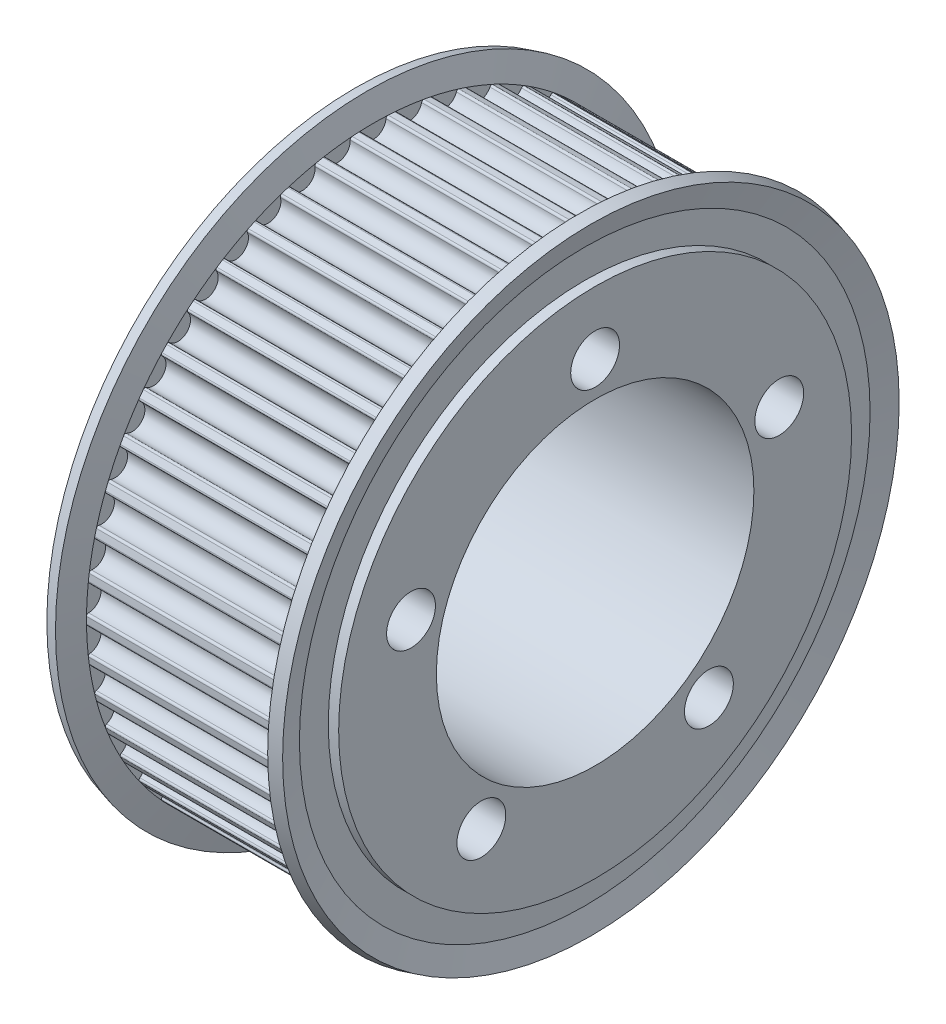
SolidWorks part; units mm, degrees
ref_plane "Front Plane" through (0, 0, 0) normal (0, 0, 1) x (1, 0, 0)
ref_plane "Top Plane" through (0, 0, 0) normal (0, 1, 0) x (1, 0, 0)
ref_plane "Right Plane" through (0, 0, 0) normal (1, 0, 0) x (0, 0, -1)
ref_plane "Plane1" through (0, 0, 0) normal (0, 0, 1) x (1, 0, 0)
sketch "Sketch1" plane through (0, 0, 0) normal (0, 0, 1) x (1, 0, 0)
  line L0 (0, 0) -> (0, 21)
  line L1 (0, 21) -> (0.85, 21)
  line L2 (0.85, 21) -> (0.85, 23.3633)
  line L3 (0.85, 23.3633) -> (0.3468, 25.2412)
  line L4 (0.3468, 25.2412) -> (1.3128, 25.5)
  line L5 (1.3128, 25.5) -> (1.85, 23.495)
  line L6 (1.85, 23.495) -> (18.15, 23.495)
  line L7 (18.15, 23.495) -> (18.6872, 25.5)
  line L8 (18.6872, 25.5) -> (19.6532, 25.2412)
  line L9 (19.6532, 25.2412) -> (19.15, 23.3633)
  line L10 (19.15, 23.3633) -> (19.15, 21)
  line L11 (19.15, 21) -> (20, 21)
  line L12 (20, 21) -> (20, 0)
  line L13 (20, 0) -> (0, 0)
  line L14 (20, 0) -> (0, 0) construction
revolve "Revolve1" add sketch "Sketch1" angle 360 about L14 reverse direction yes
ref_plane "Plane2" through (10, 0, 0) normal (1, 0, 0) x (0, 0, -1)
sketch "Sketch2" plane through (10, 0, 0) normal (1, 0, 0) x (0, 0, -1)
  line L0 (-1.2248, 23.8436) -> (-1.2053, 23.4641)
  line L1 (1.2053, 23.4641) -> (1.2248, 23.8436)
  arc A0 (-1.2053, 23.4641) -> (-1.0271, 23.3071) centre (-1.1966, 23.2943) cw
  arc A1 (-1.0271, 23.3071) -> (1.0271, 23.3071) centre (0, 23.385) ccw
  arc A2 (1.0271, 23.3071) -> (1.2053, 23.4641) centre (1.1966, 23.2943) cw
  arc A3 (1.2248, 23.8436) -> (-1.2248, 23.8436) centre (0, 0) ccw
extrude "Cut-Extrude1" cut sketch "Sketch2" against normal blind 8.15 and the other way blind 8.15
ref_plane "Plane3" through (10, 0, 0) normal (1, 0, 0) x (0, 0, -1)
sketch "Sketch3" plane through (10, 0, 0) normal (1, 0, 0) x (0, 0, -1)
  line L0 (-4.2035, 23.502) -> (-4.1366, 23.128)
  line L1 (-1.745, 23.4301) -> (-1.7733, 23.8091)
  arc A0 (-4.1366, 23.128) -> (-3.9401, 22.9946) centre (-4.1067, 22.9606) cw
  arc A1 (-3.9401, 22.9946) -> (-1.9022, 23.2521) centre (-2.9309, 23.2006) ccw
  arc A2 (-1.9022, 23.2521) -> (-1.745, 23.4301) centre (-1.7324, 23.2606) cw
  arc A3 (-1.7733, 23.8091) -> (-4.2035, 23.502) centre (0, 0) ccw
extrude "Cut-Extrude2" cut sketch "Sketch3" against normal blind 8.15 and the other way blind 8.15
ref_plane "Plane4" through (10, 0, 0) normal (1, 0, 0) x (0, 0, -1)
sketch "Sketch4" plane through (10, 0, 0) normal (1, 0, 0) x (0, 0, -1)
  line L0 (-7.116, 22.7899) -> (-7.0027, 22.4272)
  line L1 (-4.6679, 23.0266) -> (-4.7434, 23.3991)
  arc A0 (-7.0027, 22.4272) -> (-6.791, 22.3195) centre (-6.952, 22.2649) cw
  arc A1 (-6.791, 22.3195) -> (-4.8015, 22.8303) centre (-5.8156, 22.6503) ccw
  arc A2 (-4.8015, 22.8303) -> (-4.6679, 23.0266) centre (-4.6341, 22.86) cw
  arc A3 (-4.7434, 23.3991) -> (-7.116, 22.7899) centre (0, 0) ccw
extrude "Cut-Extrude3" cut sketch "Sketch4" against normal blind 8.15 and the other way blind 8.15
ref_plane "Plane5" through (10, 0, 0) normal (1, 0, 0) x (0, 0, -1)
sketch "Sketch5" plane through (10, 0, 0) normal (1, 0, 0) x (0, 0, -1)
  line L0 (-9.9162, 21.7183) -> (-9.7583, 21.3726)
  line L1 (-7.5171, 22.26) -> (-7.6386, 22.6201)
  arc A0 (-9.7583, 21.3726) -> (-9.5349, 21.2923) centre (-9.6877, 21.218) cw
  arc A1 (-9.5349, 21.2923) -> (-7.625, 22.0485) centre (-8.6086, 21.7428) ccw
  arc A2 (-7.625, 22.0485) -> (-7.5171, 22.26) centre (-7.4627, 22.099) cw
  arc A3 (-7.6386, 22.6201) -> (-9.9162, 21.7183) centre (0, 0) ccw
extrude "Cut-Extrude4" cut sketch "Sketch5" against normal blind 8.15 and the other way blind 8.15
ref_plane "Plane6" through (10, 0, 0) normal (1, 0, 0) x (0, 0, -1)
sketch "Sketch6" plane through (10, 0, 0) normal (1, 0, 0) x (0, 0, -1)
  line L0 (-12.56, 20.3042) -> (-12.3601, 19.9811)
  line L1 (-10.2477, 21.1424) -> (-10.4134, 21.4843)
  arc A0 (-12.3601, 19.9811) -> (-12.1283, 19.9294) centre (-12.2707, 19.8365) cw
  arc A1 (-12.1283, 19.9294) -> (-10.3283, 20.919) centre (-11.2658, 20.4924) ccw
  arc A2 (-10.3283, 20.919) -> (-10.2477, 21.1424) centre (-10.1735, 20.9894) cw
  arc A3 (-10.4134, 21.4843) -> (-12.56, 20.3042) centre (0, 0) ccw
extrude "Cut-Extrude5" cut sketch "Sketch6" against normal blind 8.15 and the other way blind 8.15
ref_plane "Plane7" through (10, 0, 0) normal (1, 0, 0) x (0, 0, -1)
sketch "Sketch7" plane through (10, 0, 0) normal (1, 0, 0) x (0, 0, -1)
  line L0 (-15.0058, 18.5699) -> (-14.7669, 18.2744)
  line L1 (-12.8167, 19.6913) -> (-13.024, 20.0098)
  arc A0 (-14.7669, 18.2744) -> (-14.5305, 18.2522) centre (-14.6601, 18.1422) cw
  arc A1 (-14.5305, 18.2522) -> (-12.8687, 19.4596) centre (-13.7454, 18.9189) ccw
  arc A2 (-12.8687, 19.4596) -> (-12.8167, 19.6913) centre (-12.724, 19.5488) cw
  arc A3 (-13.024, 20.0098) -> (-15.0058, 18.5699) centre (0, 0) ccw
extrude "Cut-Extrude6" cut sketch "Sketch7" against normal blind 8.15 and the other way blind 8.15
ref_plane "Plane8" through (10, 0, 0) normal (1, 0, 0) x (0, 0, -1)
sketch "Sketch8" plane through (10, 0, 0) normal (1, 0, 0) x (0, 0, -1)
  line L0 (-17.2149, 16.5428) -> (-16.9409, 16.2795)
  line L1 (-15.1836, 17.9296) -> (-15.4292, 18.2196)
  arc A0 (-16.9409, 16.2795) -> (-16.7035, 16.2871) centre (-16.8183, 16.1617) cw
  arc A1 (-16.7035, 16.2871) -> (-15.2061, 17.6932) centre (-16.0081, 17.0469) ccw
  arc A2 (-15.2061, 17.6932) -> (-15.1836, 17.9296) centre (-15.0738, 17.7999) cw
  arc A3 (-15.4292, 18.2196) -> (-17.2149, 16.5428) centre (0, 0) ccw
extrude "Cut-Extrude7" cut sketch "Sketch8" against normal blind 8.15 and the other way blind 8.15
ref_plane "Plane9" through (10, 0, 0) normal (1, 0, 0) x (0, 0, -1)
sketch "Sketch9" plane through (10, 0, 0) normal (1, 0, 0) x (0, 0, -1)
  line L0 (-19.1525, 14.2547) -> (-18.8477, 14.0279)
  line L1 (-17.3111, 15.8852) -> (-17.5911, 16.1422)
  arc A0 (-18.8477, 14.0279) -> (-18.6131, 14.0652) centre (-18.7113, 13.9264) cw
  arc A1 (-18.6131, 14.0652) -> (-17.3038, 15.6479) centre (-18.0185, 14.9062) ccw
  arc A2 (-17.3038, 15.6479) -> (-17.3111, 15.8852) centre (-17.1858, 15.7703) cw
  arc A3 (-17.5911, 16.1422) -> (-19.1525, 14.2547) centre (0, 0) ccw
extrude "Cut-Extrude8" cut sketch "Sketch9" against normal blind 8.15 and the other way blind 8.15
ref_plane "Plane10" through (10, 0, 0) normal (1, 0, 0) x (0, 0, -1)
sketch "Sketch10" plane through (10, 0, 0) normal (1, 0, 0) x (0, 0, -1)
  line L0 (-20.7881, 11.7419) -> (-20.4572, 11.555)
  line L1 (-19.1655, 13.5903) -> (-19.4755, 13.8101)
  arc A0 (-20.4572, 11.555) -> (-20.2292, 11.6214) centre (-20.3092, 11.4714) cw
  arc A1 (-20.2292, 11.6214) -> (-19.1285, 13.3558) centre (-19.7446, 12.5303) ccw
  arc A2 (-19.1285, 13.3558) -> (-19.1655, 13.5903) centre (-19.0269, 13.492) cw
  arc A3 (-19.4755, 13.8101) -> (-20.7881, 11.7419) centre (0, 0) ccw
extrude "Cut-Extrude9" cut sketch "Sketch10" against normal blind 8.15 and the other way blind 8.15
ref_plane "Plane11" through (10, 0, 0) normal (1, 0, 0) x (0, 0, -1)
sketch "Sketch11" plane through (10, 0, 0) normal (1, 0, 0) x (0, 0, -1)
  line L0 (-22.0958, 9.0439) -> (-21.7441, 8.8999)
  line L1 (-20.7177, 11.0811) -> (-21.0528, 11.2603)
  arc A0 (-21.7441, 8.8999) -> (-21.5262, 8.9944) centre (-21.5868, 8.8355) cw
  arc A1 (-21.5262, 8.9944) -> (-20.6516, 10.853) centre (-21.1594, 9.9568) ccw
  arc A2 (-20.6516, 10.853) -> (-20.7177, 11.0811) centre (-20.5678, 11.0009) cw
  arc A3 (-21.0528, 11.2603) -> (-22.0958, 9.0439) centre (0, 0) ccw
extrude "Cut-Extrude10" cut sketch "Sketch11" against normal blind 8.15 and the other way blind 8.15
ref_plane "Plane12" through (10, 0, 0) normal (1, 0, 0) x (0, 0, -1)
sketch "Sketch12" plane through (10, 0, 0) normal (1, 0, 0) x (0, 0, -1)
  line L0 (-23.0551, 6.2032) -> (-22.6881, 6.1045)
  line L1 (-21.9432, 8.3971) -> (-22.2981, 8.5329)
  arc A0 (-22.6881, 6.1045) -> (-22.4838, 6.2255) centre (-22.5239, 6.0603) cw
  arc A1 (-22.4838, 6.2255) -> (-21.849, 8.1791) centre (-22.2405, 7.2264) ccw
  arc A2 (-21.849, 8.1791) -> (-21.9432, 8.3971) centre (-21.7844, 8.3363) cw
  arc A3 (-22.2981, 8.5329) -> (-23.0551, 6.2032) centre (0, 0) ccw
extrude "Cut-Extrude11" cut sketch "Sketch12" against normal blind 8.15 and the other way blind 8.15
ref_plane "Plane13" through (10, 0, 0) normal (1, 0, 0) x (0, 0, -1)
sketch "Sketch13" plane through (10, 0, 0) normal (1, 0, 0) x (0, 0, -1)
  line L0 (-23.6507, 3.2648) -> (-23.2743, 3.2128)
  line L1 (-22.8226, 5.5807) -> (-23.1917, 5.6709)
  arc A0 (-23.2743, 3.2128) -> (-23.0868, 3.3585) centre (-23.1059, 3.1895) cw
  arc A1 (-23.0868, 3.3585) -> (-22.7019, 5.3762) centre (-22.9708, 4.3819) ccw
  arc A2 (-22.7019, 5.3762) -> (-22.8226, 5.5807) centre (-22.6575, 5.5403) cw
  arc A3 (-23.1917, 5.6709) -> (-23.6507, 3.2648) centre (0, 0) ccw
extrude "Cut-Extrude12" cut sketch "Sketch13" against normal blind 8.15 and the other way blind 8.15
ref_plane "Plane14" through (10, 0, 0) normal (1, 0, 0) x (0, 0, -1)
sketch "Sketch14" plane through (10, 0, 0) normal (1, 0, 0) x (0, 0, -1)
  line L0 (-23.8734, 0.2748) -> (-23.4934, 0.2704)
  line L1 (-23.3421, 2.6762) -> (-23.7196, 2.7195)
  arc A0 (-23.4934, 0.2704) -> (-23.3256, 0.4384) centre (-23.3235, 0.2685) cw
  arc A1 (-23.3256, 0.4384) -> (-23.1967, 2.4885) centre (-23.3389, 1.4684) ccw
  arc A2 (-23.1967, 2.4885) -> (-23.3421, 2.6762) centre (-23.1732, 2.6569) cw
  arc A3 (-23.7196, 2.7195) -> (-23.8734, 0.2748) centre (0, 0) ccw
extrude "Cut-Extrude13" cut sketch "Sketch14" against normal blind 8.15 and the other way blind 8.15
ref_plane "Plane15" through (10, 0, 0) normal (1, 0, 0) x (0, 0, -1)
sketch "Sketch15" plane through (10, 0, 0) normal (1, 0, 0) x (0, 0, -1)
  line L0 (-23.7196, -2.7195) -> (-23.3421, -2.6762)
  line L1 (-23.4934, -0.2704) -> (-23.8734, -0.2748)
  arc A0 (-23.3421, -2.6762) -> (-23.1967, -2.4885) centre (-23.1732, -2.6569) cw
  arc A1 (-23.1967, -2.4885) -> (-23.3256, -0.4384) centre (-23.3389, -1.4684) ccw
  arc A2 (-23.3256, -0.4384) -> (-23.4934, -0.2704) centre (-23.3235, -0.2685) cw
  arc A3 (-23.8734, -0.2748) -> (-23.7196, -2.7195) centre (0, 0) ccw
extrude "Cut-Extrude14" cut sketch "Sketch15" against normal blind 8.15 and the other way blind 8.15
ref_plane "Plane16" through (10, 0, 0) normal (1, 0, 0) x (0, 0, -1)
sketch "Sketch16" plane through (10, 0, 0) normal (1, 0, 0) x (0, 0, -1)
  line L0 (-23.1917, -5.6709) -> (-22.8226, -5.5807)
  line L1 (-23.2743, -3.2128) -> (-23.6507, -3.2648)
  arc A0 (-22.8226, -5.5807) -> (-22.7019, -5.3762) centre (-22.6575, -5.5403) cw
  arc A1 (-22.7019, -5.3762) -> (-23.0868, -3.3585) centre (-22.9708, -4.3819) ccw
  arc A2 (-23.0868, -3.3585) -> (-23.2743, -3.2128) centre (-23.1059, -3.1895) cw
  arc A3 (-23.6507, -3.2648) -> (-23.1917, -5.6709) centre (0, 0) ccw
extrude "Cut-Extrude15" cut sketch "Sketch16" against normal blind 8.15 and the other way blind 8.15
ref_plane "Plane17" through (10, 0, 0) normal (1, 0, 0) x (0, 0, -1)
sketch "Sketch17" plane through (10, 0, 0) normal (1, 0, 0) x (0, 0, -1)
  line L0 (-22.2981, -8.5329) -> (-21.9432, -8.3971)
  line L1 (-22.6881, -6.1045) -> (-23.0551, -6.2032)
  arc A0 (-21.9432, -8.3971) -> (-21.849, -8.1791) centre (-21.7844, -8.3363) cw
  arc A1 (-21.849, -8.1791) -> (-22.4838, -6.2255) centre (-22.2405, -7.2264) ccw
  arc A2 (-22.4838, -6.2255) -> (-22.6881, -6.1045) centre (-22.5239, -6.0603) cw
  arc A3 (-23.0551, -6.2032) -> (-22.2981, -8.5329) centre (0, 0) ccw
extrude "Cut-Extrude16" cut sketch "Sketch17" against normal blind 8.15 and the other way blind 8.15
ref_plane "Plane18" through (10, 0, 0) normal (1, 0, 0) x (0, 0, -1)
sketch "Sketch18" plane through (10, 0, 0) normal (1, 0, 0) x (0, 0, -1)
  line L0 (-21.0528, -11.2603) -> (-20.7177, -11.0811)
  line L1 (-21.7441, -8.8999) -> (-22.0958, -9.0439)
  arc A0 (-20.7177, -11.0811) -> (-20.6516, -10.853) centre (-20.5678, -11.0009) cw
  arc A1 (-20.6516, -10.853) -> (-21.5262, -8.9944) centre (-21.1594, -9.9568) ccw
  arc A2 (-21.5262, -8.9944) -> (-21.7441, -8.8999) centre (-21.5868, -8.8355) cw
  arc A3 (-22.0958, -9.0439) -> (-21.0528, -11.2603) centre (0, 0) ccw
extrude "Cut-Extrude17" cut sketch "Sketch18" against normal blind 8.15 and the other way blind 8.15
ref_plane "Plane19" through (10, 0, 0) normal (1, 0, 0) x (0, 0, -1)
sketch "Sketch19" plane through (10, 0, 0) normal (1, 0, 0) x (0, 0, -1)
  line L0 (-19.4755, -13.8101) -> (-19.1655, -13.5903)
  line L1 (-20.4572, -11.555) -> (-20.7881, -11.7419)
  arc A0 (-19.1655, -13.5903) -> (-19.1285, -13.3558) centre (-19.0269, -13.492) cw
  arc A1 (-19.1285, -13.3558) -> (-20.2292, -11.6214) centre (-19.7446, -12.5303) ccw
  arc A2 (-20.2292, -11.6214) -> (-20.4572, -11.555) centre (-20.3092, -11.4714) cw
  arc A3 (-20.7881, -11.7419) -> (-19.4755, -13.8101) centre (0, 0) ccw
extrude "Cut-Extrude18" cut sketch "Sketch19" against normal blind 8.15 and the other way blind 8.15
ref_plane "Plane20" through (10, 0, 0) normal (1, 0, 0) x (0, 0, -1)
sketch "Sketch20" plane through (10, 0, 0) normal (1, 0, 0) x (0, 0, -1)
  line L0 (-17.5911, -16.1422) -> (-17.3111, -15.8852)
  line L1 (-18.8477, -14.0279) -> (-19.1525, -14.2547)
  arc A0 (-17.3111, -15.8852) -> (-17.3038, -15.6479) centre (-17.1858, -15.7703) cw
  arc A1 (-17.3038, -15.6479) -> (-18.6131, -14.0652) centre (-18.0185, -14.9062) ccw
  arc A2 (-18.6131, -14.0652) -> (-18.8477, -14.0279) centre (-18.7113, -13.9264) cw
  arc A3 (-19.1525, -14.2547) -> (-17.5911, -16.1422) centre (0, 0) ccw
extrude "Cut-Extrude19" cut sketch "Sketch20" against normal blind 8.15 and the other way blind 8.15
ref_plane "Plane21" through (10, 0, 0) normal (1, 0, 0) x (0, 0, -1)
sketch "Sketch21" plane through (10, 0, 0) normal (1, 0, 0) x (0, 0, -1)
  line L0 (-15.4292, -18.2196) -> (-15.1836, -17.9296)
  line L1 (-16.9409, -16.2795) -> (-17.2149, -16.5428)
  arc A0 (-15.1836, -17.9296) -> (-15.2061, -17.6932) centre (-15.0738, -17.7999) cw
  arc A1 (-15.2061, -17.6932) -> (-16.7035, -16.2871) centre (-16.0081, -17.0469) ccw
  arc A2 (-16.7035, -16.2871) -> (-16.9409, -16.2795) centre (-16.8183, -16.1617) cw
  arc A3 (-17.2149, -16.5428) -> (-15.4292, -18.2196) centre (0, 0) ccw
extrude "Cut-Extrude20" cut sketch "Sketch21" against normal blind 8.15 and the other way blind 8.15
ref_plane "Plane22" through (10, 0, 0) normal (1, 0, 0) x (0, 0, -1)
sketch "Sketch22" plane through (10, 0, 0) normal (1, 0, 0) x (0, 0, -1)
  line L0 (-13.024, -20.0098) -> (-12.8167, -19.6913)
  line L1 (-14.7669, -18.2744) -> (-15.0058, -18.5699)
  arc A0 (-12.8167, -19.6913) -> (-12.8687, -19.4596) centre (-12.724, -19.5488) cw
  arc A1 (-12.8687, -19.4596) -> (-14.5305, -18.2522) centre (-13.7454, -18.9189) ccw
  arc A2 (-14.5305, -18.2522) -> (-14.7669, -18.2744) centre (-14.6601, -18.1422) cw
  arc A3 (-15.0058, -18.5699) -> (-13.024, -20.0098) centre (0, 0) ccw
extrude "Cut-Extrude21" cut sketch "Sketch22" against normal blind 8.15 and the other way blind 8.15
ref_plane "Plane23" through (10, 0, 0) normal (1, 0, 0) x (0, 0, -1)
sketch "Sketch23" plane through (10, 0, 0) normal (1, 0, 0) x (0, 0, -1)
  line L0 (-10.4134, -21.4843) -> (-10.2477, -21.1424)
  line L1 (-12.3601, -19.9811) -> (-12.56, -20.3042)
  arc A0 (-10.2477, -21.1424) -> (-10.3283, -20.919) centre (-10.1735, -20.9894) cw
  arc A1 (-10.3283, -20.919) -> (-12.1283, -19.9294) centre (-11.2658, -20.4924) ccw
  arc A2 (-12.1283, -19.9294) -> (-12.3601, -19.9811) centre (-12.2707, -19.8365) cw
  arc A3 (-12.56, -20.3042) -> (-10.4134, -21.4843) centre (0, 0) ccw
extrude "Cut-Extrude22" cut sketch "Sketch23" against normal blind 8.15 and the other way blind 8.15
ref_plane "Plane24" through (10, 0, 0) normal (1, 0, 0) x (0, 0, -1)
sketch "Sketch24" plane through (10, 0, 0) normal (1, 0, 0) x (0, 0, -1)
  line L0 (-7.6386, -22.6201) -> (-7.5171, -22.26)
  line L1 (-9.7583, -21.3726) -> (-9.9162, -21.7183)
  arc A0 (-7.5171, -22.26) -> (-7.625, -22.0485) centre (-7.4627, -22.099) cw
  arc A1 (-7.625, -22.0485) -> (-9.5349, -21.2923) centre (-8.6086, -21.7428) ccw
  arc A2 (-9.5349, -21.2923) -> (-9.7583, -21.3726) centre (-9.6877, -21.218) cw
  arc A3 (-9.9162, -21.7183) -> (-7.6386, -22.6201) centre (0, 0) ccw
extrude "Cut-Extrude23" cut sketch "Sketch24" against normal blind 8.15 and the other way blind 8.15
ref_plane "Plane25" through (10, 0, 0) normal (1, 0, 0) x (0, 0, -1)
sketch "Sketch25" plane through (10, 0, 0) normal (1, 0, 0) x (0, 0, -1)
  line L0 (-4.7434, -23.3991) -> (-4.6679, -23.0266)
  line L1 (-7.0027, -22.4272) -> (-7.116, -22.7899)
  arc A0 (-4.6679, -23.0266) -> (-4.8015, -22.8303) centre (-4.6341, -22.86) cw
  arc A1 (-4.8015, -22.8303) -> (-6.791, -22.3195) centre (-5.8156, -22.6503) ccw
  arc A2 (-6.791, -22.3195) -> (-7.0027, -22.4272) centre (-6.952, -22.2649) cw
  arc A3 (-7.116, -22.7899) -> (-4.7434, -23.3991) centre (0, 0) ccw
extrude "Cut-Extrude24" cut sketch "Sketch25" against normal blind 8.15 and the other way blind 8.15
ref_plane "Plane26" through (10, 0, 0) normal (1, 0, 0) x (0, 0, -1)
sketch "Sketch26" plane through (10, 0, 0) normal (1, 0, 0) x (0, 0, -1)
  line L0 (-1.7733, -23.8091) -> (-1.745, -23.4301)
  line L1 (-4.1366, -23.128) -> (-4.2035, -23.502)
  arc A0 (-1.745, -23.4301) -> (-1.9022, -23.2521) centre (-1.7324, -23.2606) cw
  arc A1 (-1.9022, -23.2521) -> (-3.9401, -22.9946) centre (-2.9309, -23.2006) ccw
  arc A2 (-3.9401, -22.9946) -> (-4.1366, -23.128) centre (-4.1067, -22.9606) cw
  arc A3 (-4.2035, -23.502) -> (-1.7733, -23.8091) centre (0, 0) ccw
extrude "Cut-Extrude25" cut sketch "Sketch26" against normal blind 8.15 and the other way blind 8.15
ref_plane "Plane27" through (10, 0, 0) normal (1, 0, 0) x (0, 0, -1)
sketch "Sketch27" plane through (10, 0, 0) normal (1, 0, 0) x (0, 0, -1)
  line L0 (1.2248, -23.8436) -> (1.2053, -23.4641)
  line L1 (-1.2053, -23.4641) -> (-1.2248, -23.8436)
  arc A0 (1.2053, -23.4641) -> (1.0271, -23.3071) centre (1.1966, -23.2943) cw
  arc A1 (1.0271, -23.3071) -> (-1.0271, -23.3071) centre (0, -23.385) ccw
  arc A2 (-1.0271, -23.3071) -> (-1.2053, -23.4641) centre (-1.1966, -23.2943) cw
  arc A3 (-1.2248, -23.8436) -> (1.2248, -23.8436) centre (0, 0) ccw
extrude "Cut-Extrude26" cut sketch "Sketch27" against normal blind 8.15 and the other way blind 8.15
ref_plane "Plane28" through (10, 0, 0) normal (1, 0, 0) x (0, 0, -1)
sketch "Sketch28" plane through (10, 0, 0) normal (1, 0, 0) x (0, 0, -1)
  line L0 (4.2035, -23.502) -> (4.1366, -23.128)
  line L1 (1.745, -23.4301) -> (1.7733, -23.8091)
  arc A0 (4.1366, -23.128) -> (3.9401, -22.9946) centre (4.1067, -22.9606) cw
  arc A1 (3.9401, -22.9946) -> (1.9022, -23.2521) centre (2.9309, -23.2006) ccw
  arc A2 (1.9022, -23.2521) -> (1.745, -23.4301) centre (1.7324, -23.2606) cw
  arc A3 (1.7733, -23.8091) -> (4.2035, -23.502) centre (0, 0) ccw
extrude "Cut-Extrude27" cut sketch "Sketch28" against normal blind 8.15 and the other way blind 8.15
ref_plane "Plane29" through (10, 0, 0) normal (1, 0, 0) x (0, 0, -1)
sketch "Sketch29" plane through (10, 0, 0) normal (1, 0, 0) x (0, 0, -1)
  line L0 (7.116, -22.7899) -> (7.0027, -22.4272)
  line L1 (4.6679, -23.0266) -> (4.7434, -23.3991)
  arc A0 (7.0027, -22.4272) -> (6.791, -22.3195) centre (6.952, -22.2649) cw
  arc A1 (6.791, -22.3195) -> (4.8015, -22.8303) centre (5.8156, -22.6503) ccw
  arc A2 (4.8015, -22.8303) -> (4.6679, -23.0266) centre (4.6341, -22.86) cw
  arc A3 (4.7434, -23.3991) -> (7.116, -22.7899) centre (0, 0) ccw
extrude "Cut-Extrude28" cut sketch "Sketch29" against normal blind 8.15 and the other way blind 8.15
ref_plane "Plane30" through (10, 0, 0) normal (1, 0, 0) x (0, 0, -1)
sketch "Sketch30" plane through (10, 0, 0) normal (1, 0, 0) x (0, 0, -1)
  line L0 (9.9162, -21.7183) -> (9.7583, -21.3726)
  line L1 (7.5171, -22.26) -> (7.6386, -22.6201)
  arc A0 (9.7583, -21.3726) -> (9.5349, -21.2923) centre (9.6877, -21.218) cw
  arc A1 (9.5349, -21.2923) -> (7.625, -22.0485) centre (8.6086, -21.7428) ccw
  arc A2 (7.625, -22.0485) -> (7.5171, -22.26) centre (7.4627, -22.099) cw
  arc A3 (7.6386, -22.6201) -> (9.9162, -21.7183) centre (0, 0) ccw
extrude "Cut-Extrude29" cut sketch "Sketch30" against normal blind 8.15 and the other way blind 8.15
ref_plane "Plane31" through (10, 0, 0) normal (1, 0, 0) x (0, 0, -1)
sketch "Sketch31" plane through (10, 0, 0) normal (1, 0, 0) x (0, 0, -1)
  line L0 (12.56, -20.3042) -> (12.3601, -19.9811)
  line L1 (10.2477, -21.1424) -> (10.4134, -21.4843)
  arc A0 (12.3601, -19.9811) -> (12.1283, -19.9294) centre (12.2707, -19.8365) cw
  arc A1 (12.1283, -19.9294) -> (10.3283, -20.919) centre (11.2658, -20.4924) ccw
  arc A2 (10.3283, -20.919) -> (10.2477, -21.1424) centre (10.1735, -20.9894) cw
  arc A3 (10.4134, -21.4843) -> (12.56, -20.3042) centre (0, 0) ccw
extrude "Cut-Extrude30" cut sketch "Sketch31" against normal blind 8.15 and the other way blind 8.15
ref_plane "Plane32" through (10, 0, 0) normal (1, 0, 0) x (0, 0, -1)
sketch "Sketch32" plane through (10, 0, 0) normal (1, 0, 0) x (0, 0, -1)
  line L0 (15.0058, -18.5699) -> (14.7669, -18.2744)
  line L1 (12.8167, -19.6913) -> (13.024, -20.0098)
  arc A0 (14.7669, -18.2744) -> (14.5305, -18.2522) centre (14.6601, -18.1422) cw
  arc A1 (14.5305, -18.2522) -> (12.8687, -19.4596) centre (13.7454, -18.9189) ccw
  arc A2 (12.8687, -19.4596) -> (12.8167, -19.6913) centre (12.724, -19.5488) cw
  arc A3 (13.024, -20.0098) -> (15.0058, -18.5699) centre (0, 0) ccw
extrude "Cut-Extrude31" cut sketch "Sketch32" against normal blind 8.15 and the other way blind 8.15
ref_plane "Plane33" through (10, 0, 0) normal (1, 0, 0) x (0, 0, -1)
sketch "Sketch33" plane through (10, 0, 0) normal (1, 0, 0) x (0, 0, -1)
  line L0 (17.2149, -16.5428) -> (16.9409, -16.2795)
  line L1 (15.1836, -17.9296) -> (15.4292, -18.2196)
  arc A0 (16.9409, -16.2795) -> (16.7035, -16.2871) centre (16.8183, -16.1617) cw
  arc A1 (16.7035, -16.2871) -> (15.2061, -17.6932) centre (16.0081, -17.0469) ccw
  arc A2 (15.2061, -17.6932) -> (15.1836, -17.9296) centre (15.0738, -17.7999) cw
  arc A3 (15.4292, -18.2196) -> (17.2149, -16.5428) centre (0, 0) ccw
extrude "Cut-Extrude32" cut sketch "Sketch33" against normal blind 8.15 and the other way blind 8.15
ref_plane "Plane34" through (10, 0, 0) normal (1, 0, 0) x (0, 0, -1)
sketch "Sketch34" plane through (10, 0, 0) normal (1, 0, 0) x (0, 0, -1)
  line L0 (19.1525, -14.2547) -> (18.8477, -14.0279)
  line L1 (17.3111, -15.8852) -> (17.5911, -16.1422)
  arc A0 (18.8477, -14.0279) -> (18.6131, -14.0652) centre (18.7113, -13.9264) cw
  arc A1 (18.6131, -14.0652) -> (17.3038, -15.6479) centre (18.0185, -14.9062) ccw
  arc A2 (17.3038, -15.6479) -> (17.3111, -15.8852) centre (17.1858, -15.7703) cw
  arc A3 (17.5911, -16.1422) -> (19.1525, -14.2547) centre (0, 0) ccw
extrude "Cut-Extrude33" cut sketch "Sketch34" against normal blind 8.15 and the other way blind 8.15
ref_plane "Plane35" through (10, 0, 0) normal (1, 0, 0) x (0, 0, -1)
sketch "Sketch35" plane through (10, 0, 0) normal (1, 0, 0) x (0, 0, -1)
  line L0 (20.7881, -11.7419) -> (20.4572, -11.555)
  line L1 (19.1655, -13.5903) -> (19.4755, -13.8101)
  arc A0 (20.4572, -11.555) -> (20.2292, -11.6214) centre (20.3092, -11.4714) cw
  arc A1 (20.2292, -11.6214) -> (19.1285, -13.3558) centre (19.7446, -12.5303) ccw
  arc A2 (19.1285, -13.3558) -> (19.1655, -13.5903) centre (19.0269, -13.492) cw
  arc A3 (19.4755, -13.8101) -> (20.7881, -11.7419) centre (0, 0) ccw
extrude "Cut-Extrude34" cut sketch "Sketch35" against normal blind 8.15 and the other way blind 8.15
ref_plane "Plane36" through (10, 0, 0) normal (1, 0, 0) x (0, 0, -1)
sketch "Sketch36" plane through (10, 0, 0) normal (1, 0, 0) x (0, 0, -1)
  line L0 (22.0958, -9.0439) -> (21.7441, -8.8999)
  line L1 (20.7177, -11.0811) -> (21.0528, -11.2603)
  arc A0 (21.7441, -8.8999) -> (21.5262, -8.9944) centre (21.5868, -8.8355) cw
  arc A1 (21.5262, -8.9944) -> (20.6516, -10.853) centre (21.1594, -9.9568) ccw
  arc A2 (20.6516, -10.853) -> (20.7177, -11.0811) centre (20.5678, -11.0009) cw
  arc A3 (21.0528, -11.2603) -> (22.0958, -9.0439) centre (0, 0) ccw
extrude "Cut-Extrude35" cut sketch "Sketch36" against normal blind 8.15 and the other way blind 8.15
ref_plane "Plane37" through (10, 0, 0) normal (1, 0, 0) x (0, 0, -1)
sketch "Sketch37" plane through (10, 0, 0) normal (1, 0, 0) x (0, 0, -1)
  line L0 (23.0551, -6.2032) -> (22.6881, -6.1045)
  line L1 (21.9432, -8.3971) -> (22.2981, -8.5329)
  arc A0 (22.6881, -6.1045) -> (22.4838, -6.2255) centre (22.5239, -6.0603) cw
  arc A1 (22.4838, -6.2255) -> (21.849, -8.1791) centre (22.2405, -7.2264) ccw
  arc A2 (21.849, -8.1791) -> (21.9432, -8.3971) centre (21.7844, -8.3363) cw
  arc A3 (22.2981, -8.5329) -> (23.0551, -6.2032) centre (0, 0) ccw
extrude "Cut-Extrude36" cut sketch "Sketch37" against normal blind 8.15 and the other way blind 8.15
ref_plane "Plane38" through (10, 0, 0) normal (1, 0, 0) x (0, 0, -1)
sketch "Sketch38" plane through (10, 0, 0) normal (1, 0, 0) x (0, 0, -1)
  line L0 (23.6507, -3.2648) -> (23.2743, -3.2128)
  line L1 (22.8226, -5.5807) -> (23.1917, -5.6709)
  arc A0 (23.2743, -3.2128) -> (23.0868, -3.3585) centre (23.1059, -3.1895) cw
  arc A1 (23.0868, -3.3585) -> (22.7019, -5.3762) centre (22.9708, -4.3819) ccw
  arc A2 (22.7019, -5.3762) -> (22.8226, -5.5807) centre (22.6575, -5.5403) cw
  arc A3 (23.1917, -5.6709) -> (23.6507, -3.2648) centre (0, 0) ccw
extrude "Cut-Extrude37" cut sketch "Sketch38" against normal blind 8.15 and the other way blind 8.15
ref_plane "Plane39" through (10, 0, 0) normal (1, 0, 0) x (0, 0, -1)
sketch "Sketch39" plane through (10, 0, 0) normal (1, 0, 0) x (0, 0, -1)
  line L0 (23.8734, -0.2748) -> (23.4934, -0.2704)
  line L1 (23.3421, -2.6762) -> (23.7196, -2.7195)
  arc A0 (23.4934, -0.2704) -> (23.3256, -0.4384) centre (23.3235, -0.2685) cw
  arc A1 (23.3256, -0.4384) -> (23.1967, -2.4885) centre (23.3389, -1.4684) ccw
  arc A2 (23.1967, -2.4885) -> (23.3421, -2.6762) centre (23.1732, -2.6569) cw
  arc A3 (23.7196, -2.7195) -> (23.8734, -0.2748) centre (0, 0) ccw
extrude "Cut-Extrude38" cut sketch "Sketch39" against normal blind 8.15 and the other way blind 8.15
ref_plane "Plane40" through (10, 0, 0) normal (1, 0, 0) x (0, 0, -1)
sketch "Sketch40" plane through (10, 0, 0) normal (1, 0, 0) x (0, 0, -1)
  line L0 (23.7196, 2.7195) -> (23.3421, 2.6762)
  line L1 (23.4934, 0.2704) -> (23.8734, 0.2748)
  arc A0 (23.3421, 2.6762) -> (23.1967, 2.4885) centre (23.1732, 2.6569) cw
  arc A1 (23.1967, 2.4885) -> (23.3256, 0.4384) centre (23.3389, 1.4684) ccw
  arc A2 (23.3256, 0.4384) -> (23.4934, 0.2704) centre (23.3235, 0.2685) cw
  arc A3 (23.8734, 0.2748) -> (23.7196, 2.7195) centre (0, 0) ccw
extrude "Cut-Extrude39" cut sketch "Sketch40" against normal blind 8.15 and the other way blind 8.15
ref_plane "Plane41" through (10, 0, 0) normal (1, 0, 0) x (0, 0, -1)
sketch "Sketch41" plane through (10, 0, 0) normal (1, 0, 0) x (0, 0, -1)
  line L0 (23.1917, 5.6709) -> (22.8226, 5.5807)
  line L1 (23.2743, 3.2128) -> (23.6507, 3.2648)
  arc A0 (22.8226, 5.5807) -> (22.7019, 5.3762) centre (22.6575, 5.5403) cw
  arc A1 (22.7019, 5.3762) -> (23.0868, 3.3585) centre (22.9708, 4.3819) ccw
  arc A2 (23.0868, 3.3585) -> (23.2743, 3.2128) centre (23.1059, 3.1895) cw
  arc A3 (23.6507, 3.2648) -> (23.1917, 5.6709) centre (0, 0) ccw
extrude "Cut-Extrude40" cut sketch "Sketch41" against normal blind 8.15 and the other way blind 8.15
ref_plane "Plane42" through (10, 0, 0) normal (1, 0, 0) x (0, 0, -1)
sketch "Sketch42" plane through (10, 0, 0) normal (1, 0, 0) x (0, 0, -1)
  line L0 (22.2981, 8.5329) -> (21.9432, 8.3971)
  line L1 (22.6881, 6.1045) -> (23.0551, 6.2032)
  arc A0 (21.9432, 8.3971) -> (21.849, 8.1791) centre (21.7844, 8.3363) cw
  arc A1 (21.849, 8.1791) -> (22.4838, 6.2255) centre (22.2405, 7.2264) ccw
  arc A2 (22.4838, 6.2255) -> (22.6881, 6.1045) centre (22.5239, 6.0603) cw
  arc A3 (23.0551, 6.2032) -> (22.2981, 8.5329) centre (0, 0) ccw
extrude "Cut-Extrude41" cut sketch "Sketch42" against normal blind 8.15 and the other way blind 8.15
ref_plane "Plane43" through (10, 0, 0) normal (1, 0, 0) x (0, 0, -1)
sketch "Sketch43" plane through (10, 0, 0) normal (1, 0, 0) x (0, 0, -1)
  line L0 (21.0528, 11.2603) -> (20.7177, 11.0811)
  line L1 (21.7441, 8.8999) -> (22.0958, 9.0439)
  arc A0 (20.7177, 11.0811) -> (20.6516, 10.853) centre (20.5678, 11.0009) cw
  arc A1 (20.6516, 10.853) -> (21.5262, 8.9944) centre (21.1594, 9.9568) ccw
  arc A2 (21.5262, 8.9944) -> (21.7441, 8.8999) centre (21.5868, 8.8355) cw
  arc A3 (22.0958, 9.0439) -> (21.0528, 11.2603) centre (0, 0) ccw
extrude "Cut-Extrude42" cut sketch "Sketch43" against normal blind 8.15 and the other way blind 8.15
ref_plane "Plane44" through (10, 0, 0) normal (1, 0, 0) x (0, 0, -1)
sketch "Sketch44" plane through (10, 0, 0) normal (1, 0, 0) x (0, 0, -1)
  line L0 (19.4755, 13.8101) -> (19.1655, 13.5903)
  line L1 (20.4572, 11.555) -> (20.7881, 11.7419)
  arc A0 (19.1655, 13.5903) -> (19.1285, 13.3558) centre (19.0269, 13.492) cw
  arc A1 (19.1285, 13.3558) -> (20.2292, 11.6214) centre (19.7446, 12.5303) ccw
  arc A2 (20.2292, 11.6214) -> (20.4572, 11.555) centre (20.3092, 11.4714) cw
  arc A3 (20.7881, 11.7419) -> (19.4755, 13.8101) centre (0, 0) ccw
extrude "Cut-Extrude43" cut sketch "Sketch44" against normal blind 8.15 and the other way blind 8.15
ref_plane "Plane45" through (10, 0, 0) normal (1, 0, 0) x (0, 0, -1)
sketch "Sketch45" plane through (10, 0, 0) normal (1, 0, 0) x (0, 0, -1)
  line L0 (17.5911, 16.1422) -> (17.3111, 15.8852)
  line L1 (18.8477, 14.0279) -> (19.1525, 14.2547)
  arc A0 (17.3111, 15.8852) -> (17.3038, 15.6479) centre (17.1858, 15.7703) cw
  arc A1 (17.3038, 15.6479) -> (18.6131, 14.0652) centre (18.0185, 14.9062) ccw
  arc A2 (18.6131, 14.0652) -> (18.8477, 14.0279) centre (18.7113, 13.9264) cw
  arc A3 (19.1525, 14.2547) -> (17.5911, 16.1422) centre (0, 0) ccw
extrude "Cut-Extrude44" cut sketch "Sketch45" against normal blind 8.15 and the other way blind 8.15
ref_plane "Plane46" through (10, 0, 0) normal (1, 0, 0) x (0, 0, -1)
sketch "Sketch46" plane through (10, 0, 0) normal (1, 0, 0) x (0, 0, -1)
  line L0 (15.4292, 18.2196) -> (15.1836, 17.9296)
  line L1 (16.9409, 16.2795) -> (17.2149, 16.5428)
  arc A0 (15.1836, 17.9296) -> (15.2061, 17.6932) centre (15.0738, 17.7999) cw
  arc A1 (15.2061, 17.6932) -> (16.7035, 16.2871) centre (16.0081, 17.0469) ccw
  arc A2 (16.7035, 16.2871) -> (16.9409, 16.2795) centre (16.8183, 16.1617) cw
  arc A3 (17.2149, 16.5428) -> (15.4292, 18.2196) centre (0, 0) ccw
extrude "Cut-Extrude45" cut sketch "Sketch46" against normal blind 8.15 and the other way blind 8.15
ref_plane "Plane47" through (10, 0, 0) normal (1, 0, 0) x (0, 0, -1)
sketch "Sketch47" plane through (10, 0, 0) normal (1, 0, 0) x (0, 0, -1)
  line L0 (13.024, 20.0098) -> (12.8167, 19.6913)
  line L1 (14.7669, 18.2744) -> (15.0058, 18.5699)
  arc A0 (12.8167, 19.6913) -> (12.8687, 19.4596) centre (12.724, 19.5488) cw
  arc A1 (12.8687, 19.4596) -> (14.5305, 18.2522) centre (13.7454, 18.9189) ccw
  arc A2 (14.5305, 18.2522) -> (14.7669, 18.2744) centre (14.6601, 18.1422) cw
  arc A3 (15.0058, 18.5699) -> (13.024, 20.0098) centre (0, 0) ccw
extrude "Cut-Extrude46" cut sketch "Sketch47" against normal blind 8.15 and the other way blind 8.15
ref_plane "Plane48" through (10, 0, 0) normal (1, 0, 0) x (0, 0, -1)
sketch "Sketch48" plane through (10, 0, 0) normal (1, 0, 0) x (0, 0, -1)
  line L0 (10.4134, 21.4843) -> (10.2477, 21.1424)
  line L1 (12.3601, 19.9811) -> (12.56, 20.3042)
  arc A0 (10.2477, 21.1424) -> (10.3283, 20.919) centre (10.1735, 20.9894) cw
  arc A1 (10.3283, 20.919) -> (12.1283, 19.9294) centre (11.2658, 20.4924) ccw
  arc A2 (12.1283, 19.9294) -> (12.3601, 19.9811) centre (12.2707, 19.8365) cw
  arc A3 (12.56, 20.3042) -> (10.4134, 21.4843) centre (0, 0) ccw
extrude "Cut-Extrude47" cut sketch "Sketch48" against normal blind 8.15 and the other way blind 8.15
ref_plane "Plane49" through (10, 0, 0) normal (1, 0, 0) x (0, 0, -1)
sketch "Sketch49" plane through (10, 0, 0) normal (1, 0, 0) x (0, 0, -1)
  line L0 (7.6386, 22.6201) -> (7.5171, 22.26)
  line L1 (9.7583, 21.3726) -> (9.9162, 21.7183)
  arc A0 (7.5171, 22.26) -> (7.625, 22.0485) centre (7.4627, 22.099) cw
  arc A1 (7.625, 22.0485) -> (9.5349, 21.2923) centre (8.6086, 21.7428) ccw
  arc A2 (9.5349, 21.2923) -> (9.7583, 21.3726) centre (9.6877, 21.218) cw
  arc A3 (9.9162, 21.7183) -> (7.6386, 22.6201) centre (0, 0) ccw
extrude "Cut-Extrude48" cut sketch "Sketch49" against normal blind 8.15 and the other way blind 8.15
ref_plane "Plane50" through (10, 0, 0) normal (1, 0, 0) x (0, 0, -1)
sketch "Sketch50" plane through (10, 0, 0) normal (1, 0, 0) x (0, 0, -1)
  line L0 (4.7434, 23.3991) -> (4.6679, 23.0266)
  line L1 (7.0027, 22.4272) -> (7.116, 22.7899)
  arc A0 (4.6679, 23.0266) -> (4.8015, 22.8303) centre (4.6341, 22.86) cw
  arc A1 (4.8015, 22.8303) -> (6.791, 22.3195) centre (5.8156, 22.6503) ccw
  arc A2 (6.791, 22.3195) -> (7.0027, 22.4272) centre (6.952, 22.2649) cw
  arc A3 (7.116, 22.7899) -> (4.7434, 23.3991) centre (0, 0) ccw
extrude "Cut-Extrude49" cut sketch "Sketch50" against normal blind 8.15 and the other way blind 8.15
ref_plane "Plane51" through (10, 0, 0) normal (1, 0, 0) x (0, 0, -1)
sketch "Sketch51" plane through (10, 0, 0) normal (1, 0, 0) x (0, 0, -1)
  line L0 (1.7733, 23.8091) -> (1.745, 23.4301)
  line L1 (4.1366, 23.128) -> (4.2035, 23.502)
  arc A0 (1.745, 23.4301) -> (1.9022, 23.2521) centre (1.7324, 23.2606) cw
  arc A1 (1.9022, 23.2521) -> (3.9401, 22.9946) centre (2.9309, 23.2006) ccw
  arc A2 (3.9401, 22.9946) -> (4.1366, 23.128) centre (4.1067, 22.9606) cw
  arc A3 (4.2035, 23.502) -> (1.7733, 23.8091) centre (0, 0) ccw
extrude "Cut-Extrude50" cut sketch "Sketch51" against normal blind 8.15 and the other way blind 8.15
ref_plane "Plane52" through (0, 0, 0) normal (0, 0, 1) x (1, 0, 0)
sketch "Sketch52" plane through (0, 0, 0) normal (0, 0, 1) x (1, 0, 0)
  line L0 (0, 0) -> (0, 13)
  line L1 (0, 13) -> (20, 13)
  line L2 (20, 13) -> (20, 0)
  line L3 (20, 0) -> (0, 0)
  line L4 (20, 0) -> (0, 0) construction
  dimension "D1" = 13
revolve "Cut-Revolve1" cut sketch "Sketch52" angle 360 about L4 reverse direction yes
sketch "Sketch53" plane through (0, 0, 0) normal (-1, 0, 0) x (0, 0, 1)
  circle A0 centre (0, 15.85) radius 2
  circle A1 centre (15.0742, 4.8979) radius 2
  circle A2 centre (9.3164, -12.8229) radius 2
  circle A3 centre (-9.3164, -12.8229) radius 2
  circle A4 centre (-15.0742, 4.8979) radius 2
  point P14 (0, 0)
  dimension "D1" = 15.85
  dimension "D2" = 5
extrude "Cut-Extrude51" cut sketch "Sketch53" against normal through all
